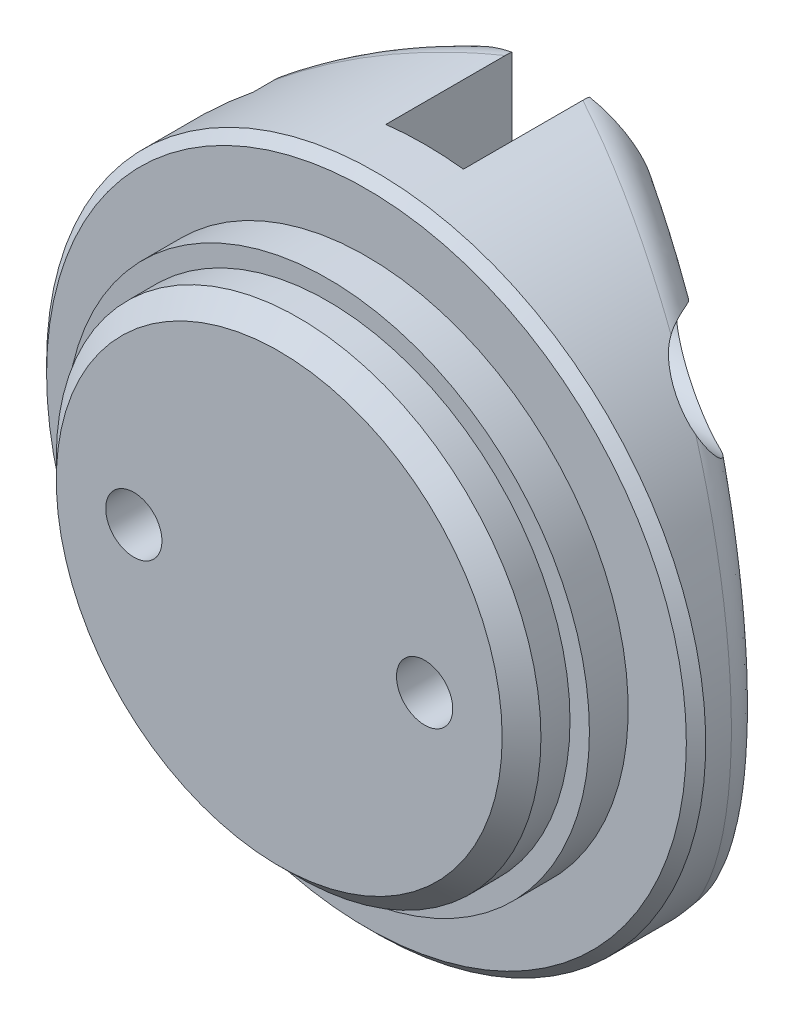
SolidWorks part; units mm, degrees
ref_plane "Front Plane" through (0, 0, 0) normal (0, 0, 1) x (1, 0, 0)
ref_plane "Top Plane" through (0, 0, 0) normal (0, 1, 0) x (1, 0, 0)
ref_plane "Right Plane" through (0, 0, 0) normal (1, 0, 0) x (0, 0, -1)
sketch "Sketch1" plane through (0, 0, 0) normal (0, 0, 1) x (1, 0, 0)
  circle A0 centre (0, 0) radius 12.5
  dimension "D1" = 25
extrude "Boss-Extrude1" add sketch "Sketch1" along normal blind 4.5
sketch "Sketch2" plane through (0, 0, 0) normal (0, 0, -1) x (-1, 0, 0)
  circle A0 centre (0, 0) radius 17
  dimension "D1" = 34
extrude "Boss-Extrude2" add sketch "Sketch2" along normal blind 3
chamfer "Chamfer1" distance 1 angle 45 1 edges at (12.5, 0, 4.5)
sketch "Sketch3" plane through (0, 0, 0) normal (0, 1, 0) x (1, 0, 0)
  line L0 (0, 0) -> (0, 9.5) construction
  line L1 (-17, 3) -> (-5.274, 9.5)
  line L2 (-5.274, 9.5) -> (-2, 9.5)
  line L3 (-2, 9.5) -> (-2, 3)
  line L4 (17, 3) -> (-17, 3) construction
  line L5 (-17, 3) -> (-2, 3)
  line L6 (17, 3) -> (2, 3)
  line L7 (2, 9.5) -> (2, 3)
  line L8 (5.274, 9.5) -> (2, 9.5)
  line L9 (17, 3) -> (5.274, 9.5)
  dimension "D1" = 4
  dimension "D2" = 6.5
extrude "Boss-Extrude3" add sketch "Sketch3" along normal mid plane 40
sketch "Sketch4" plane through (0, 0, 0) normal (1, 0, 0) x (0, 0, -1)
  line L0 (5.75, 11) -> (5.75, -11) construction
  line L1 (9.5, 20) -> (9.5, -20) construction
  circle A0 centre (5.75, 11) radius 1.25
  circle A1 centre (5.75, -11) radius 1.25
  point P4 (5.75, 0)
  dimension "D1" = 2.5
  dimension "D2" = 22
  dimension "D3" = 3.75
extrude "Cut-Extrude1" cut sketch "Sketch4" against normal through all both and the other way through all
sketch "Sketch5" plane through (0, 0, 0) normal (0, 0, 1) x (1, 0, 0)
  circle A0 centre (0, 0) radius 13.5
  dimension "D1" = 27
extrude "Boss-Extrude4" add sketch "Sketch5" along normal blind 2
sketch "Sketch6" plane through (0, 0, 4.5) normal (0, 0, 1) x (1, 0, 0)
  line L1 (23.3622, -22.945) -> (-23.3622, -22.945)
  line L2 (23.3622, -22.945) -> (23.3622, 22.945)
  line L3 (23.3622, 22.945) -> (-23.3622, 22.945)
  line L4 (-23.3622, -22.945) -> (-23.3622, 22.945)
  line L5 (23.3622, -22.945) -> (-23.3622, 22.945) construction
  line L6 (23.3622, 22.945) -> (-23.3622, -22.945) construction
  circle A0 centre (0, 0) radius 17
  arc A1 (2, -16.8819) -> (17, 0) centre (0, 0) ccw construction
extrude "Cut-Extrude2" cut sketch "Sketch6" against normal through all both and the other way through all
sketch "Sketch7" plane through (0, 0, -3) normal (0, 0, -1) x (-1, 0, 0)
  line L0 (2, 16.8819) -> (2, -16.8819) construction
  line L1 (-2, 7) -> (2, 7)
  line L2 (-2, 7) -> (-2, -7)
  line L3 (-2, -7) -> (2, -7)
  line L4 (2, 7) -> (2, -7)
  line L5 (-2, 7) -> (2, -7) construction
  line L6 (-2, -7) -> (2, 7) construction
  point P0 (0, 0)
  dimension "D1" = 14
extrude "Cut-Extrude3" cut sketch "Sketch7" against normal blind 3
sketch "Sketch8" plane through (0, 0, 0) normal (1, 0, 0) x (0, 0, -1)
  circle A0 centre (5.75, 11) radius 2.25
  circle A1 centre (5.75, -11) radius 2.25
  dimension "D1" = 4.5
extrude "Cut-Extrude4" cut sketch "Sketch8" along normal blind 33 from offset 6
sketch "Sketch9" plane through (0, 0, 0) normal (1, 0, 0) x (0, 0, -1)
  line L1 (7.3377, 8.25) -> (8.9254, 11)
  line L2 (8.9254, 11) -> (7.3377, 13.75)
  line L3 (7.3377, 13.75) -> (4.1623, 13.75)
  line L4 (4.1623, 13.75) -> (2.5746, 11)
  line L5 (2.5746, 11) -> (4.1623, 8.25)
  line L6 (4.1623, 8.25) -> (7.3377, 8.25)
  line L7 (4.1623, -13.75) -> (7.3377, -13.75)
  line L8 (7.3377, -13.75) -> (8.9254, -11)
  line L9 (8.9254, -11) -> (7.3377, -8.25)
  line L10 (7.3377, -8.25) -> (4.1623, -8.25)
  line L11 (4.1623, -8.25) -> (2.5746, -11)
  line L12 (2.5746, -11) -> (4.1623, -13.75)
  circle A0 centre (5.75, 11) radius 2.75 construction
  circle A1 centre (5.75, -11) radius 2.75 construction
  dimension "D1" = 5.5
extrude "Cut-Extrude5" cut sketch "Sketch9" against normal blind 33 from offset 5 offset against normal yes
fillet "Fillet1" radius 2 6 edges at (8.1708, 14.9076, -7.8942) (17, 0, -3) (8.1708, -14.9076, -7.8942) (-7.73, -15.1409, -8.1386) (-7.73, 15.1409, -8.1386) (-17, 0, -3)
chamfer "Chamfer2" distance 0.5 angle 45 1 edges at (-17, 0, 0)
sketch "Sketch10" plane through (0, 0, 0) normal (1, 0, 0) x (0, 0, -1)
  circle A0 centre (35, 0) radius 28
  dimension "D1" = 56
  dimension "D2" = 35
extrude "Cut-Extrude6" cut sketch "Sketch10" against normal blind 10 from offset 6 offset against normal yes
sketch "Sketch11" plane through (0, 0, 4.5) normal (0, 0, 1) x (1, 0, 0)
  line L0 (0, 6.9351) -> (0, -4.8401) construction
  circle A0 centre (-7.5, 0) radius 1.45
  circle A1 centre (7.5, 0) radius 1.45
  dimension "D1" = 2.9
  dimension "D2" = 15
extrude "Cut-Extrude7" cut sketch "Sketch11" against normal blind 10
fillet "Fillet2" radius 1.4 2 edges at (-6.05, 0, -5.5) (6.05, 0, -5.5)
